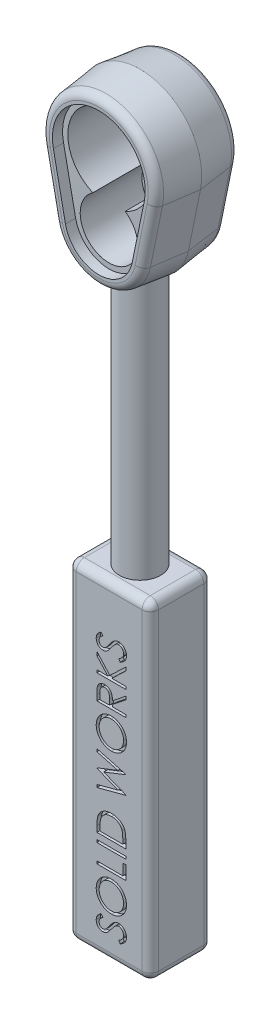
SolidWorks part; units mm, degrees
ref_plane "Front Plane" through (0, 0, 0) normal (0, 0, 1) x (1, 0, 0)
ref_plane "Top Plane" through (0, 0, 0) normal (0, 1, 0) x (1, 0, 0)
ref_plane "Right Plane" through (0, 0, 0) normal (1, 0, 0) x (0, 0, -1)
sketch "Sketch2" plane through (0, 0, 0) normal (0, 0, 1) x (1, 0, 0)
  line L0 (0, 0) -> (0, 0.7337) construction
  line L1 (-0.7348, 0.6) -> (-0.5879, -0.12)
  line L2 (0.7348, 0.6) -> (0.5879, -0.12)
  arc A0 (-0.7348, 0.6) -> (0.7348, 0.6) centre (0, 0.75) cw
  arc A1 (0.5879, -0.12) -> (-0.5879, -0.12) centre (0, 0) cw
  point P8 (0, 0)
  point P9 (0, -0.2221)
  dimension "D1" = 0.75
  dimension "D2" = 0.6
  dimension "D3" = 0.75
extrude "Boss-Extrude1" add sketch "Sketch2" along normal mid plane 1 draft 7
sketch "Sketch4" plane through (0, 0, 0.5) normal (0, 0, 1) x (1, 0, 0)
  line L4 (-0.5522, 0.6373) -> (-0.4053, -0.0827)
  line L5 (0.4053, -0.0827) -> (0.5522, 0.6373)
  line L6 (-0.5522, 0.6373) -> (-0.4053, -0.0827)
  line L7 (0.4053, -0.0827) -> (0.5522, 0.6373)
  arc A4 (0.5522, 0.6373) -> (-0.5522, 0.6373) centre (0, 0.75) ccw
  arc A5 (-0.4053, -0.0827) -> (0.4053, -0.0827) centre (0, 0) ccw
  arc A6 (0.5522, 0.6373) -> (-0.5522, 0.6373) centre (0, 0.75) ccw
  arc A7 (-0.4053, -0.0827) -> (0.4053, -0.0827) centre (0, 0) ccw
  dimension "D1" = 0.125
extrude "Cut-Extrude1" cut sketch "Sketch4" against normal blind 0.1235
sketch "Sketch5" plane through (0, 0, 0.3765) normal (0, 0, 1) x (1, 0, 0)
  arc A0 (-0.196, 0.29) -> (0.196, 0.29) centre (0, 0) ccw
  arc A1 (0.196, 0.29) -> (-0.196, 0.29) centre (0, 0.75) ccw
  dimension "D1" = 0.7
  dimension "D2" = 1
extrude "Cut-Extrude2" cut sketch "Sketch5" against normal blind 0.75
sketch "Sketch6" plane through (0, 0, -0.3735) normal (0, 0, 1) x (1, 0, 0)
  circle A0 centre (0, 0) radius 0.175
  circle A1 centre (0, 0.75) radius 0.175
  dimension "D1" = 0.35
extrude "Cut-Extrude3" cut sketch "Sketch6" against normal through all
fillet "Fillet3" radius 0.1 4 edges at (-0.6012, 0.2523, 0.5) (0, 1.4386, 0.5) (0.6012, 0.2523, 0.5) (0, -0.5386, 0.5)
fillet "Fillet4" radius 0.1 4 edges at (0, -0.5386, -0.5) (0.6012, 0.2523, -0.5) (0, 1.4386, -0.5) (-0.6012, 0.2523, -0.5)
ref_plane "Plane1" through (0, -4, 0) normal (0, 1, 0) x (1, 0, 0)
sketch "Sketch7" plane through (0, -4, 0) normal (0, 1, 0) x (1, 0, 0)
  circle A0 centre (0, 0) radius 0.25
  dimension "D1" = 0.5
extrude "Boss-Extrude2" add sketch "Sketch7" along normal up to next
sketch "Sketch8" plane through (0, 0, 0) normal (0, 0, 1) x (1, 0, 0)
  line L6 (-0.5, -3.7) -> (0.5, -3.7)
  line L7 (-0.5, -3.7) -> (-0.5, -7.7)
  line L8 (-0.5, -7.7) -> (0.5, -7.7)
  line L9 (0.5, -3.7) -> (0.5, -7.7)
  point P4 (0, -3.7)
  dimension "D1" = 1
  dimension "D2" = 4
  dimension "D3" = 3.7
extrude "Boss-Extrude3" add sketch "Sketch8" along normal mid plane 0.75
fillet "Fillet5" radius 0.1 6 edges at (0.5, -7.7, 0) (0.5, -5.7, 0.375) (0.5, -3.7, 0) (0.5, -5.7, -0.375) (-0.5, -5.7, 0.375) (-0.5, -5.7, -0.375)
fillet "Fillet6" radius 0.1 14 edges at (0.4707, -3.7293, 0.3457) (0.4707, -3.7293, -0.3457) (0, -3.7, -0.375) (-0.4707, -3.7, -0.3457) (-0.5, -3.7, 0) (-0.4707, -3.7, 0.3457) (0.4707, -7.6707, -0.3457) (0, -7.7, -0.375) (-0.4707, -7.7, -0.3457) (-0.5, -7.7, 0) (-0.4707, -7.7, 0.3457) (0.4707, -7.6707, 0.3457) (0, -3.7, 0.375) (0, -7.7, 0.375)
sketch "Sketch9" plane through (0, 0, 0.375) normal (0, 0, 1) x (1, 0, 0)
  line L0 (0.2021, -7.4546) -> (0.2021, -3.9615) construction
  text T0 "SOLID WORKS\r\n" font "Century Gothic" height 0.35
extrude "Cut-Extrude6" cut sketch "Sketch9" against normal blind 0.05
